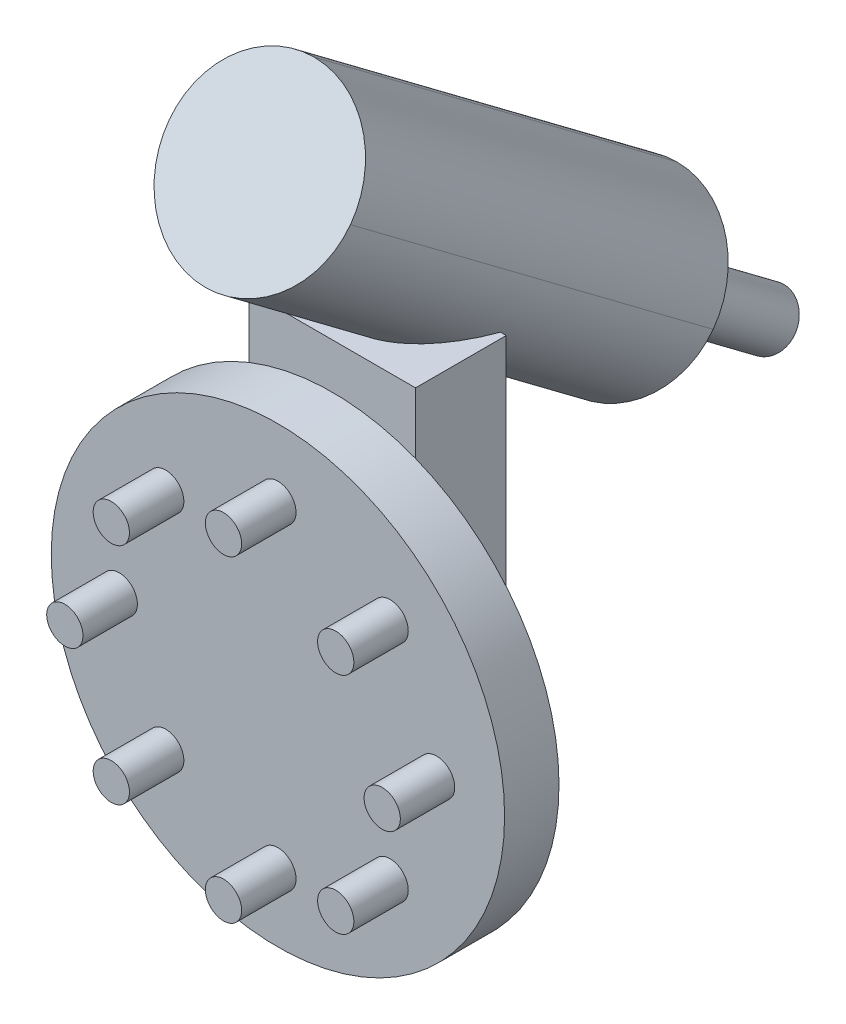
SolidWorks part; units mm, degrees
ref_plane "Ebene vorne" through (0, 0, 0) normal (0, 0, 1) x (1, 0, 0)
ref_plane "Ebene oben" through (0, 0, 0) normal (0, 1, 0) x (1, 0, 0)
ref_plane "Ebene rechts" through (0, 0, 0) normal (1, 0, 0) x (0, 0, -1)
sketch "Skizze2" plane through (0, 0, 0) normal (0, 0, 1) x (1, 0, 0)
  circle A0 centre (0, 0) radius 12.5
extrude "Aufsatz-Linear austragen1" add sketch "Skizze2" along normal blind 3
sketch "Skizze3" plane through (0, 0, 3) normal (0, 0, 1) x (1, 0, 0)
  circle A0 centre (0, 8.75) radius 1
  circle A1 centre (6.1872, 6.1872) radius 1
  circle A2 centre (8.75, 0) radius 1
  circle A3 centre (6.1872, -6.1872) radius 1
  circle A4 centre (0, -8.75) radius 1
  circle A5 centre (-6.1872, -6.1872) radius 1
  circle A6 centre (-8.75, 0) radius 1
  circle A7 centre (-6.1872, 6.1872) radius 1
  point P20 (0, 0)
  dimension "D1" = 8.75
  dimension "D2" = 2
  dimension "D3" = 8
extrude "Aufsatz-Linear austragen2" add sketch "Skizze3" along normal blind 3
sketch "Skizze4" plane through (0, 0, 0) normal (0, 0, -1) x (-1, 0, 0)
  line L5 (-4.5879, 0) -> (4.5879, 0)
  line L6 (-4.5879, 0) -> (-4.5879, 15)
  line L7 (-4.5879, 15) -> (4.5879, 15)
  line L8 (4.5879, 0) -> (4.5879, 15)
  line L9 (-4.5879, 0) -> (4.5879, 15) construction
  line L10 (-4.5879, 15) -> (4.5879, 0) construction
  point P0 (0, 7.5)
  point P5 (0, 0)
  dimension "D1" = 15
extrude "Aufsatz-Linear austragen3" add sketch "Skizze4" along normal blind 5
sketch "Skizze5" plane through (4.5879, 0, 0) normal (1, 0, 0) x (0, 0, -1)
  line L2 (1, 15) -> (5, 15)
  line L5 (5, 15) -> (0, 15) construction
  line L6 (5, 15) -> (5, 12)
  line L7 (5, 15) -> (5, 0) construction
  line L8 (5, 12) -> (1, 15)
  dimension "D1" = 4
  dimension "D2" = 3
extrude "Schnitt-Linear austragen1" cut sketch "Skizze5" against normal blind 10
sketch "Skizze6" plane through (0, 10.08, -7.56) normal (0, 0.8, -0.6) x (1, 0, 0)
  line L0 (0, -3.2) -> (0, -8.2) construction
  line L1 (-5, -18.2) -> (5, -18.2)
  line L2 (-5, -18.2) -> (-5, 6.8)
  line L3 (-5, 6.8) -> (5, 6.8)
  line L4 (5, -18.2) -> (5, 6.8)
  line L5 (-5, -18.2) -> (5, 6.8) construction
  line L6 (-5, 6.8) -> (5, -18.2) construction
  line L7 (-4.5879, -3.2) -> (4.5879, -3.2) construction
  line L8 (-4.5879, -8.2) -> (4.5879, -8.2) construction
  point P0 (0, -5.7)
  point P11 (0, -5.7)
  dimension "D1" = 10
  dimension "D2" = 25
extrude "Aufsatz-Linear austragen4" add sketch "Skizze6" along normal blind 10
fillet "Verrundung1" radius 5 4 edges at (5, 13.5, -3) (-5, 13.5, -3) (-5, 21.5, -9) (5, 21.5, -9)
sketch "Skizze7" plane through (0, -4.08, -5.44) normal (0, -0.6, -0.8) x (-1, 0, 0)
  circle A0 centre (0, 17.6) radius 1.5
extrude "Aufsatz-Linear austragen5" add sketch "Skizze7" along normal blind 10
